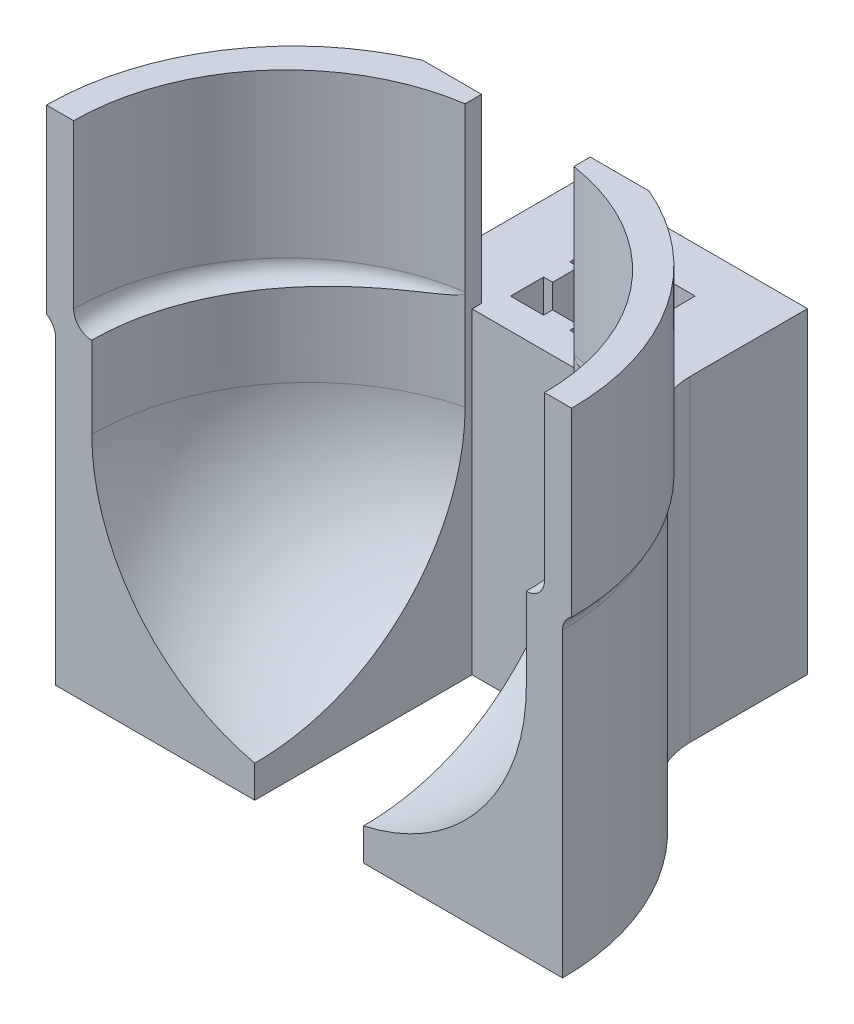
SolidWorks part; units mm, degrees
ref_plane "Front Plane" through (0, 0, 0) normal (0, 0, 1) x (1, 0, 0)
ref_plane "Top Plane" through (0, 0, 0) normal (0, 1, 0) x (1, 0, 0)
ref_plane "Right Plane" through (0, 0, 0) normal (1, 0, 0) x (0, 0, -1)
ref_axis "Axe1" through (0, -1.5691, 0) along (0, 1, 0)
sketch "Esquisse2" plane through (0, 0, 0) normal (-1, 0, 0) x (0, 0, 1)
  line L0 (-24, 35) -> (-28, 35)
  line L1 (-28, 35) -> (-28, 0)
  line L2 (-28, 0) -> (0, 0)
  line L3 (-1, 3) -> (0, 3)
  line L4 (-24, 35) -> (-24, 26)
  line L6 (0, 3) -> (0, 0)
  line L7 (0, -1.5691) -> (0, 32.9511) construction
  arc A0 (-24, 26) -> (-1, 3) centre (-1, 26) ccw
  dimension "D3" = 23
  dimension "D1" = 4
  dimension "D2" = 1
  dimension "D4" = 35
  dimension "D5" = 3
revolve "Révolution1" add sketch "Esquisse2" angle 180 mid plane about axis through (0, -1.5691, 0) along (0, 1, 0)
sketch "Esquisse3" plane through (0, 35, 0) normal (0, -1, 0) x (1, 0, 0)
  line L1 (-6, 0) -> (6, 0)
  line L2 (-6, 0) -> (-6, -24)
  line L3 (-6, -24) -> (6, -24)
  line L4 (6, 0) -> (6, -24)
  line L8 (-6, -27.3496) -> (6, -27.3496)
  line L9 (-6, -27.3496) -> (-6, -28)
  line L10 (-6, -28) -> (6, -28)
  line L11 (6, -27.3496) -> (6, -28)
  arc A0 (-28, 0) -> (28, 0) centre (0, 0) ccw construction
  arc A1 (-24, 0) -> (24, 0) centre (0, 0) ccw construction
  point P6 (0, 0)
  dimension "D1" = 12
extrude "Launcher Hole" cut sketch "Esquisse3" along normal through all
sketch "Esquisse4" plane through (0, 0, 0) normal (0, -1, 0) x (-1, 0, 0)
  line L0 (-6, 27.3496) -> (6, 27.3496) construction
  line L1 (1.45, 27.3496) -> (5.1, 27.3496)
  line L2 (1.45, 27.3496) -> (1.45, 28.3496)
  line L3 (1.45, 28.3496) -> (-1.45, 28.3496)
  line L4 (-1.45, 27.3496) -> (-1.45, 28.3496)
  line L5 (5.1, 27.3496) -> (5.1, 30.9996)
  line L6 (5.1, 30.9996) -> (4.1, 30.9996)
  line L7 (4.1, 30.9996) -> (4.1, 33.8996)
  line L8 (4.1, 33.8996) -> (5.1, 33.8996)
  line L9 (5.1, 33.8996) -> (5.1, 37.5496)
  line L10 (5.1, 37.5496) -> (1.45, 37.5496)
  line L11 (1.45, 37.5496) -> (1.45, 36.5496)
  line L12 (1.45, 36.5496) -> (-1.45, 36.5496)
  line L13 (-1.45, 36.5496) -> (-1.45, 37.5496)
  line L14 (-1.45, 37.5496) -> (-5.1, 37.5496)
  line L15 (-5.1, 37.5496) -> (-5.1, 33.8996)
  line L16 (-5.1, 33.8996) -> (-4.1, 33.8996)
  line L17 (-4.1, 33.8996) -> (-4.1, 30.9996)
  line L18 (-4.1, 30.9996) -> (-5.1, 30.9996)
  line L19 (-5.1, 30.9996) -> (-5.1, 27.3496)
  line L20 (-5.1, 27.3496) -> (-1.45, 27.3496)
  line L21 (5.1, 30.9996) -> (12.5, 30.9996) construction
  line L22 (12.5, 24) -> (-12.5, 24)
  line L23 (12.5, 24) -> (12.5, 42.5496)
  line L24 (12.5, 42.5496) -> (-12.5, 42.5496)
  line L25 (-12.5, 24) -> (-12.5, 42.5496)
  line L26 (-5.1, 30.9996) -> (-12.5, 30.9996) construction
  line L27 (6, 24) -> (-6, 24) construction
  point P7 (0, 27.3496)
  point P40 (0, 28.3496)
  dimension "D1" = 2.9
  dimension "D2" = 1
  dimension "D3" = 10.2
  dimension "D4" = 10.2
  dimension "D5" = 5
  dimension "D6" = 25
extrude "Fixing Support" add sketch "Esquisse4" against normal through all
sketch "Esquisse5" plane through (0, 0, -42.5496) normal (0, 0, -1) x (-1, 0, 0)
  line L3 (0, -1.5691) -> (0, 32.9511) construction
  line L4 (6, 0) -> (-6, 0) construction
  line L5 (6, 35) -> (-6, 35) construction
  circle A0 centre (0, 5) radius 1.6
  circle A1 centre (0, 30) radius 1.6
  dimension "D1" = 3.2
  dimension "D2" = 5
  dimension "D3" = 5
extrude "Fixing Hole" cut sketch "Esquisse5" against normal up to next
sketch "Esquisse7" plane through (0, 0, -42.5496) normal (0, 0, -1) x (-1, 0, 0)
  circle A0 centre (0, 30) radius 4.25
  circle A1 centre (0, 5) radius 4.25
  dimension "D1" = 8.5
extrude "Fixing Screw Hole" cut sketch "Esquisse7" against normal blind 2
sketch "Esquisse6" plane through (-12.5, 0, 0) normal (-1, 0, 0) x (0, 0, 1)
  line L2 (-42.5496, 35) -> (-42.5496, 0) construction
  line L3 (-25.0549, 35) -> (-42.5496, 35) construction
  circle A0 centre (-32.5496, 30) radius 2.3
  dimension "D1" = 4.6
  dimension "D2" = 10
  dimension "D3" = 5
extrude "Ressort Hole" cut sketch "Esquisse6" against normal blind 7
sketch "Esquisse8" plane through (0, 35, 0) normal (0, 1, 0) x (1, 0, 0)
  line L0 (6, 23.2379) -> (6, 25.0549)
  line L1 (6, 25.0549) -> (12.5, 25.0549)
  line L2 (26, 0) -> (29, 0)
  line L3 (12.5, 42.5496) -> (12.5, 25.0549) construction
  line L5 (6, 23.2379) -> (6, 0) construction
  line L6 (24, 0) -> (28, 0) construction
  line L7 (6, 0) -> (24, 0) construction
  arc A0 (12.5, 25.0549) -> (29, 0) centre (1.7273, 0) cw
  arc A1 (26, 0) -> (6, 23.2379) centre (2.5, 0) ccw
  arc A2 (28, 0) -> (12.5, 25.0549) centre (0, 0) ccw construction
  arc A3 (24, 0) -> (6, 23.2379) centre (0, 0) ccw construction
  arc A4 (24, 0) -> (6, 23.2379) centre (0, 0) ccw construction
  point P2 (12.1538, 25.2247)
  point P4 (12.4949, 25.0575)
  point P13 (28, 0)
  point P14 (29.3228, 0)
  point P17 (0, 0)
  dimension "D1" = 3
extrude "EndExtrusion" add sketch "Esquisse8" along normal blind 20
fillet "Congé2" radius 8 2 edges at (-12.5, 17.5, -25.0549) (12.5, 17.5, -25.0549)
fillet "Fillet2" radius 2 2 edges at (20.3115, 35, -15.3297) (24.8037, 35, -12.9915)
mirror "Mirror2" about plane through (0, 0, 0) normal (1, 0, 0) of bodies 112
